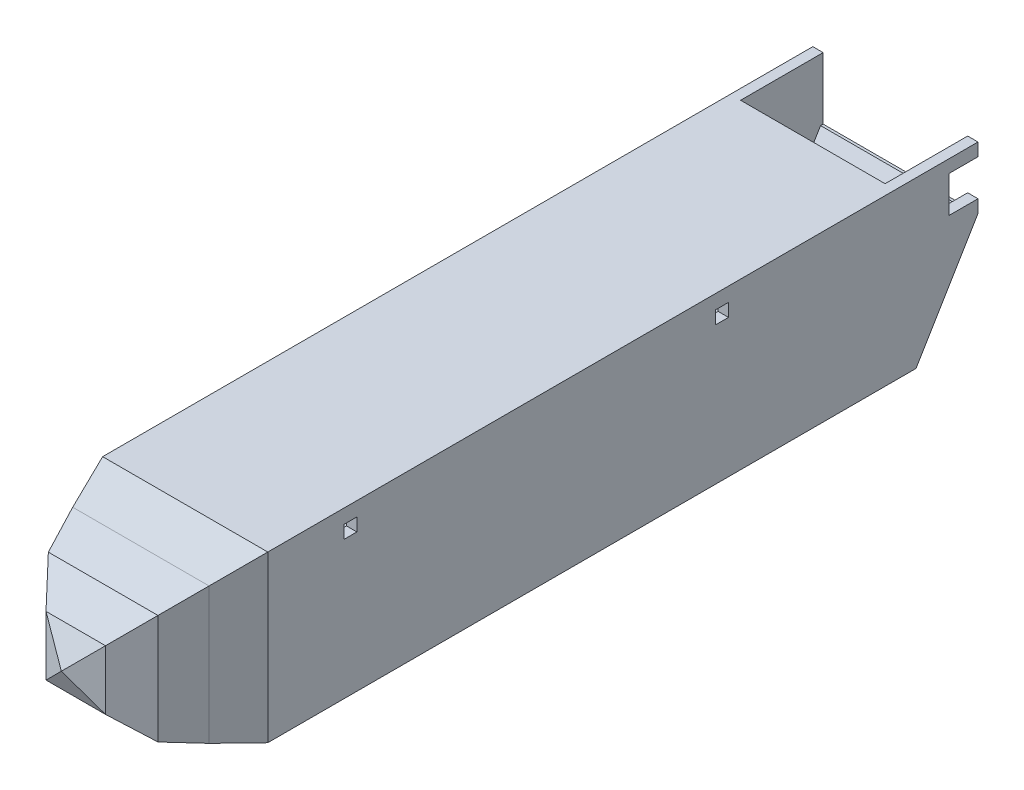
SolidWorks part; units mm, degrees
material "Balsa"
ref_plane "Front Plane" through (0, 0, 0) normal (0, 0, 1) x (1, 0, 0)
ref_plane "Top Plane" through (0, 0, 0) normal (0, 1, 0) x (1, 0, 0)
ref_plane "Right Plane" through (0, 0, 0) normal (1, 0, 0) x (0, 0, -1)
sketch "Sketch1" plane through (0, 0, 0) normal (0, 0, 1) x (1, 0, 0)
  line L1 (-50.8, -50.8) -> (50.8, -50.8)
  line L2 (-50.8, -50.8) -> (-50.8, 50.8)
  line L3 (-50.8, 50.8) -> (50.8, 50.8)
  line L4 (50.8, -50.8) -> (50.8, 50.8)
  line L5 (-50.8, -50.8) -> (50.8, 50.8) construction
  line L6 (-50.8, 50.8) -> (50.8, -50.8) construction
  point P0 (0, 0)
  dimension "D1" = 101.6
extrude "Boss-Extrude1" add sketch "Sketch1" along normal blind 436.88 contours L2 L1 L4 L3
ref_plane "Plane1" through (0, 0, 464.1566) normal (0, 0, 1) x (1, 0, 0)
sketch "Sketch3" plane through (0, 0, 464.1566) normal (0, 0, 1) x (1, 0, 0)
  line L1 (-41.9373, -41.9373) -> (41.9373, -41.9373)
  line L2 (-41.9373, -41.9373) -> (-41.9373, 41.9373)
  line L3 (-41.9373, 41.9373) -> (41.9373, 41.9373)
  line L4 (41.9373, -41.9373) -> (41.9373, 41.9373)
  line L5 (-41.9373, -41.9373) -> (41.9373, 41.9373) construction
  line L6 (-41.9373, 41.9373) -> (41.9373, -41.9373) construction
  point P0 (0, 0)
  dimension "D1" = 83.8746
  dimension "D2" = 83.8746
sketch "Sketch5" plane through (0, 0, 436.88) normal (0, 0, 1) x (1, 0, 0)
  line L0 (50.8, -50.8) -> (50.8, 50.8) construction
  line L1 (-50.8, 50.8) -> (50.8, 50.8) construction
  line L2 (-50.8, -50.8) -> (-50.8, 50.8) construction
  line L3 (-50.8, -50.8) -> (50.8, -50.8) construction
  line L4 (50.8, -50.8) -> (50.8, 50.8)
  line L5 (-50.8, 50.8) -> (50.8, 50.8)
  line L6 (-50.8, -50.8) -> (-50.8, 50.8)
  line L7 (-50.8, -50.8) -> (50.8, -50.8)
  dimension "D1" = 101.6
  dimension "D2" = 101.6
loft "Loft2" add profiles "Sketch5", "Sketch3" connector at (-50.8, 50.8, 436.88) connector at (-41.9373, 41.9373, 464.1566)
ref_plane "Plane2" through (0, 0, 487.3594) normal (0, 0, 1) x (1, 0, 0)
sketch "Sketch6" plane through (0, 0, 487.3594) normal (0, 0, 1) x (1, 0, 0)
  line L1 (-33.716, -33.716) -> (33.716, -33.716)
  line L2 (-33.716, -33.716) -> (-33.716, 33.716)
  line L3 (-33.716, 33.716) -> (33.716, 33.716)
  line L4 (33.716, -33.716) -> (33.716, 33.716)
  line L5 (-33.716, -33.716) -> (33.716, 33.716) construction
  line L6 (-33.716, 33.716) -> (33.716, -33.716) construction
  point P0 (0, 0)
loft "Loft3" add profiles "Sketch3<6>", "Sketch6" connector at (-41.9373, 41.9373, 464.1566) connector at (-33.716, 33.716, 487.3594)
sketch "Sketch3<6>" plane through (0, 0, 464.1566) normal (0, 0, 1) x (1, 0, 0) same geometry as "Sketch3"
ref_plane "Plane3" through (0, 0, 504.2173) normal (0, 0, 1) x (1, 0, 0)
sketch "Sketch7" plane through (0, 0, 504.2173) normal (0, 0, 1) x (1, 0, 0)
  line L5 (-41.9373, -41.9373) -> (41.9373, 41.9373) construction
  line L6 (-18.3041, -18.3041) -> (18.3041, -18.3041)
  line L8 (-18.3041, -18.3041) -> (-18.3041, 18.3041)
  line L9 (-18.3041, 18.3041) -> (18.3041, 18.3041)
  line L10 (18.3041, -18.3041) -> (18.3041, 18.3041)
  line L11 (-18.3041, -18.3041) -> (18.3041, 18.3041) construction
  line L12 (-18.3041, 18.3041) -> (18.3041, -18.3041) construction
  point P1 (0, 0)
loft "Loft4" add profiles "Sketch6<4>", "Sketch7" connector at (33.716, 33.716, 487.3594) connector at (18.3041, 18.3041, 504.2173)
sketch "Sketch6<4>" plane through (0, 0, 487.3594) normal (0, 0, 1) x (1, 0, 0) same geometry as "Sketch6"
sketch3d "3DSketch1" plane through (0, 0, 0) normal (0, 0, 1) x (1, 0, 0)
  dimension "D1" = 8.8627
sketch "Sketch8" plane through (0, 0, 513.08) normal (0, 0, 1) x (1, 0, 0)
  point P0 (0, 0)
loft "Loft5" add profiles "Sketch8", "Sketch7<5>"
sketch "Sketch7<5>" plane through (0, 0, 504.2173) normal (0, 0, 1) x (1, 0, 0) same geometry as "Sketch7"
shell "Shell1" thickness 6.35 removed face at (0, 0, 0)
sketch "Sketch9" plane through (50.8, 0, 0) normal (1, 0, 0) x (0, 0, -1)
  line L0 (-436.88, 50.8) -> (-436.88, 38.1)
  line L1 (-436.88, -50.8) -> (-436.88, 50.8) construction
  line L2 (-436.88, 38.1) -> (-386.08, 38.1)
  line L3 (-386.08, 38.1) -> (-157.48, 38.1)
  line L5 (-390.0805, 34.0995) -> (-382.0795, 34.0995)
  line L6 (-390.0805, 34.0995) -> (-390.0805, 42.1005)
  line L7 (-390.0805, 42.1005) -> (-382.0795, 42.1005)
  line L8 (-382.0795, 34.0995) -> (-382.0795, 42.1005)
  line L9 (-390.0805, 34.0995) -> (-382.0795, 42.1005) construction
  line L10 (-390.0805, 42.1005) -> (-382.0795, 34.0995) construction
  line L11 (-161.4805, 34.0995) -> (-153.4795, 34.0995)
  line L12 (-161.4805, 34.0995) -> (-161.4805, 42.1005)
  line L13 (-161.4805, 42.1005) -> (-153.4795, 42.1005)
  line L14 (-153.4795, 34.0995) -> (-153.4795, 42.1005)
  line L15 (-161.4805, 34.0995) -> (-153.4795, 42.1005) construction
  line L16 (-161.4805, 42.1005) -> (-153.4795, 34.0995) construction
  dimension "D4" = 8.001
  dimension "D5" = 8.001
  dimension "D1" = 12.7
  dimension "D2" = 50.8
  dimension "D3" = 228.6
  dimension "D6" = 8.001
  dimension "D7" = 8.001
extrude "Cut-Extrude1" cut sketch "Sketch9" against normal through all contours L5 L8 L3 L2 L6 | L3 L8 L7 L6 L2 | L11 L14 L13 L12 region at (50.8, 40.1002, 386.08) region at (50.8, 36.0997, 386.08) region at (50.8, 40.1002, 161.3673)
sketch "Sketch10" plane through (50.8, 0, 0) normal (1, 0, 0) x (0, 0, -1)
  line L0 (-436.88, 50.8) -> (0, 50.8) construction
  line L3 (0, 50.8) -> (-68.9584, 50.8)
  line L4 (-68.9584, -50.8) -> (-68.9584, 50.8)
  line L5 (0, 50.8) -> (0, 12.7)
  line L6 (0, -50.8) -> (-38.1, -50.8)
  line L7 (0, 12.7) -> (-38.1, -50.8)
  line L8 (0, 12.7) -> (0, -50.8)
  line M16 (0, -50.8) -> (0, 50.8)
  line M19 (-436.88, -50.8) -> (0, -50.8)
  dimension "D1" = 38.1
  dimension "D2" = 38.1
  dimension "D3" = 63.5
extrude "Cut-Extrude2" cut sketch "Sketch10" against normal through all contours L7 M16 M19 region at (50.8, -29.6333, 12.7)
sketch "Sketch11" plane through (50.8, 0, 0) normal (1, 0, 0) x (0, 0, -1)
  line L0 (-38.1, -50.8) -> (-39.6875, -50.8)
  line L1 (-436.88, -50.8) -> (-38.1, -50.8) construction
  line L2 (0, 50.8) -> (-1.5875, 50.8)
  line L3 (-436.88, 50.8) -> (0, 50.8) construction
  line L4 (-1.5875, 50.8) -> (-1.5875, 12.7)
  line L5 (0, 50.8) -> (0, 12.7)
  line L6 (-1.5875, 12.7) -> (-39.6875, -50.8)
  line L7 (0, 12.7) -> (-38.1, -50.8)
  dimension "D1" = 1.5875
  dimension "D2" = 1.5875
extrude "Boss-Extrude2" add sketch "Sketch11" against normal blind 101.6
sketch "Sketch12" plane through (0, 0, 0) normal (0, 0, -1) x (-1, 0, 0)
  line L0 (-50.8, 50.8) -> (-44.45, 50.8)
  line L1 (50.8, 50.8) -> (-50.8, 50.8) construction
  line L2 (50.8, 12.7) -> (-50.8, 12.7) construction
  line L3 (-44.45, 50.8) -> (44.45, 50.8)
  line L4 (-44.45, 50.8) -> (-44.45, 12.7)
  line L5 (-44.45, 12.7) -> (44.45, 12.7)
  line L6 (44.45, 50.8) -> (44.45, 12.7)
  line M7 (-50.8, 12.7) -> (50.8, 12.7)
  line M9 (50.8, 50.8) -> (-50.8, 50.8)
  dimension "D1" = 6.35
  dimension "D2" = 88.9
extrude "Cut-Extrude3" cut sketch "Sketch12" against normal blind 50.8 contours L6 L4 M9 M7 region at (0, 31.75, 0)
sketch "Sketch15" plane through (50.8, 0, 0) normal (1, 0, 0) x (0, 0, -1)
  line L0 (0, 12.7) -> (0, 50.8) construction
  line L1 (0, 42.926) -> (-17.78, 42.926)
  line L2 (0, 42.926) -> (0, 20.574)
  line L3 (0, 20.574) -> (-17.78, 20.574)
  line L4 (-17.78, 42.926) -> (-17.78, 20.574)
  line L5 (-436.88, 50.8) -> (0, 50.8) construction
  dimension "D1" = 17.78
  dimension "D2" = 22.352
  dimension "D3" = 7.874
extrude "Cut-Extrude5" cut sketch "Sketch15" against normal up to surface (6.35 mm away)
equation "\"Fuse_Diam\"= 4"
equation "\"D2@Sketch1\"=\"Fuse_Diam\""
equation "\"D1@Sketch1\"=\"Fuse_Diam\""
equation "\"Magic Line\"= 3 / ( cos ( 18 ) + cos ( 2 * 18 ) + cos ( 3 * 18 ) + cos ( 4 * 18 ) )"
equation "\"Second Stage Cone\"= 3.30215"
equation "\"D1@Sketch3\"=\"Second Stage Cone\""
equation "\"D2@Sketch3\"=\"Second Stage Cone\""
equation "\"Thick\"=0.25"
equation "\"D1@Sketch12\"=\"Thick\""
equation "\"D1@Shell1\"=\"Thick\""
equation "\"attachment\"=3.5"
equation "\"D2@Sketch12\"=\"attachment\""
